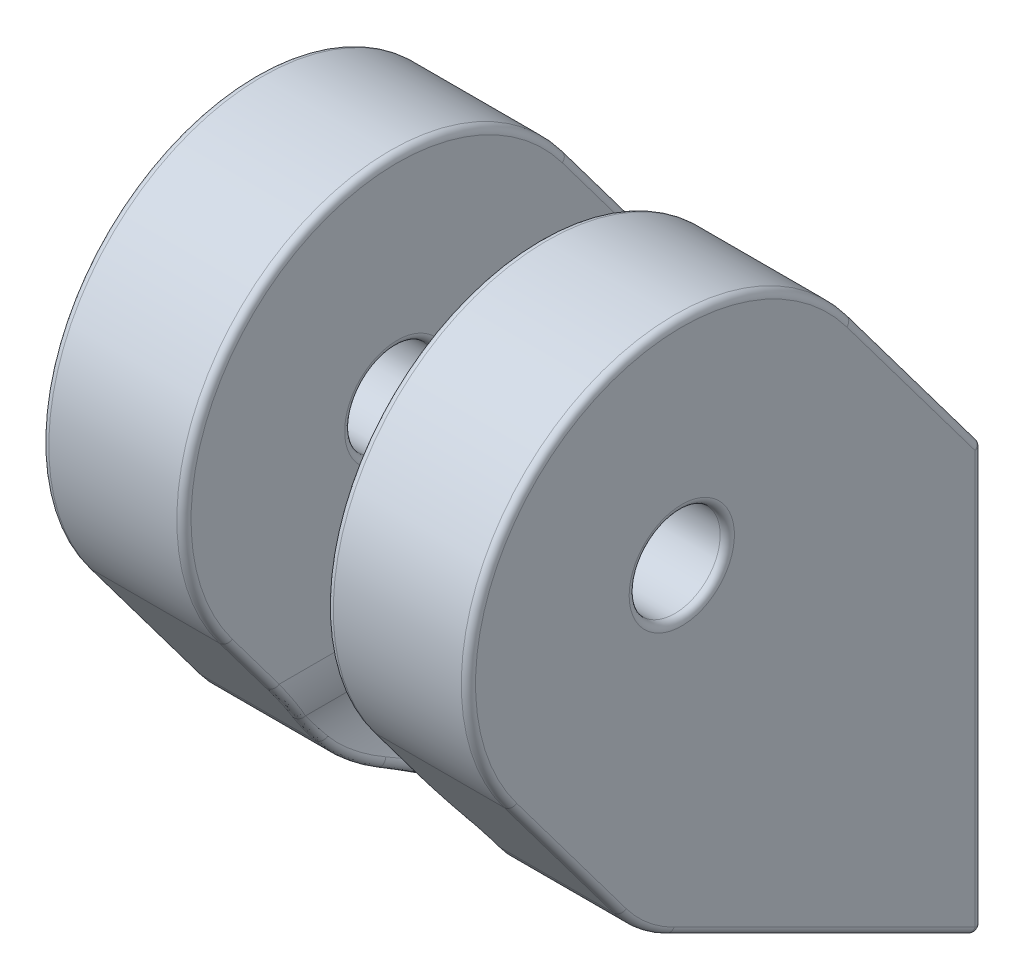
SolidWorks part; units mm, degrees
ref_plane "Front Plane" through (0, 0, 0) normal (1, 0, 0) x (0, 1, 0)
ref_plane "Top Plane" through (0, 0, 0) normal (0, 0, 1) x (0, 1, 0)
ref_plane "Right Plane" through (0, 0, 0) normal (0, 1, 0) x (-1, 0, 0)
sketch "Sketch1" plane through (0, 0, 0) normal (1, 0, 0) x (0, 1, 0)
  line L0 (30, 0) -> (0, 0)
  line L1 (0, 0) -> (12, 24)
  line L7 (30, 0) -> (12, 24)
  line L8 (30, 0) -> (42.16, 9.12)
  line L9 (24.16, 33.12) -> (12, 24)
  circle A1 centre (33.16, 21.12) radius 3.2
  arc A2 (42.16, 9.12) -> (24.16, 33.12) centre (33.16, 21.12) ccw
  arc A3 (29.4, 0.8) -> (29, 0) centre (29, 0.5) cw
  point P11 (15, 0)
  point P12 (21, 0)
  point P15 (21, 12)
  dimension "D2" = 6.4
  dimension "D3" = 30
  dimension "D4" = 15.2
  dimension "D7" = 0.5
  dimension "D1" = 30
  dimension "D5" = 6
  dimension "D6" = 12
extrude "Boss-Extrude1" add sketch "Sketch1" against normal blind 15 contours L7 L1 A1 | L1 L0 L7 | L7 A3 L0 region at (0, 29.5973, 0.2013) region at (0, 30.1089, 0.7067) region at (0, 13.9903, 8.0048)
extrude "Cut-Extrude5" cut sketch "Sketch1<3>" against normal blind 5 contours L7 L1 A1 | L7 A3 L0 region at (0, 29.5973, 0.2013) region at (0, 30.1089, 0.7067)
sketch "Sketch1<3>" plane through (0, 0, 0) normal (1, 0, 0) x (0, 1, 0) same geometry as "Sketch1"
sketch "Sketch4" plane through (0, 0, 0) normal (0, 0, -1) x (1, 0, 0)
  line L0 (0, -29) -> (0, 0) construction
  circle A0 centre (0, -14.5) radius 3.2
  circle A1 centre (0, -14.5) radius 6
  line M1 (0, -29) -> (0, 0)
  dimension "D1" = 12
  dimension "D2" = 6.4
extrude "Cut-Extrude6" cut sketch "Sketch4" against normal through all contours A0 M1 region at (-1.3581, 14.5, 0)
extrude "Cut-Extrude7" cut sketch "Sketch4<3>" against normal through all from offset 6 contours A1 A0 M1 region at (-3.3342, 14.5, 0) offset against normal yes
sketch "Sketch4<3>" plane through (0, 0, 0) normal (0, 0, -1) x (1, 0, 0) same geometry as "Sketch4"
mirror "Mirror1" about plane through (0, 0, 0) normal (1, 0, 0) of bodies 108
fillet "Fillet1" radius 10 4 edges at (-5, 17.8166, 22.3035) (5, 17.8166, 22.3035) (10.2272, 12, 24) (-10.2272, 12, 24)
fillet "Fillet3" radius 1 1 edges at (0, 20.5, 12.6667)
fillet "Fillet4" radius 0.5 33 edges at (-15, 36.08, 4.56) (-15, 5.4721, 10.9443) (-15, 12.211, 23.8239) (-15, 19.0243, 29.2682) (15, 36.08, 4.56) (15, 5.4721, 10.9443) (15, 12.211, 23.8239) (15, 19.0243, 29.2682) (5, 36.08, 4.56) (5, 45.16, 30.12) (5, 22.1139, 31.5854) (5.1575, 18.3, 28.725) (-5, 36.08, 4.56) (-5, 45.16, 30.12) (-5, 22.1139, 31.5854) (-5.1575, 18.3, 28.725) (-5.9519, 15.258, 26.4435) (-5.353, 11.7897, 23.2823) (0, 8.5, 17) (5.6938, 12.6076, 24.2712) (0, 17.7, 0) (-15, 33.16, 17.92) (5, 33.16, 17.92) (-5, 33.16, 17.92) (15, 33.16, 17.92) (-15, 15, 0) (15, 15, 0) (0, 0, 0) (-10, 30, 0) (10, 30, 0) (-15, 45.16, 30.12) (15, 45.16, 30.12) (5.9519, 15.258, 26.4435)
